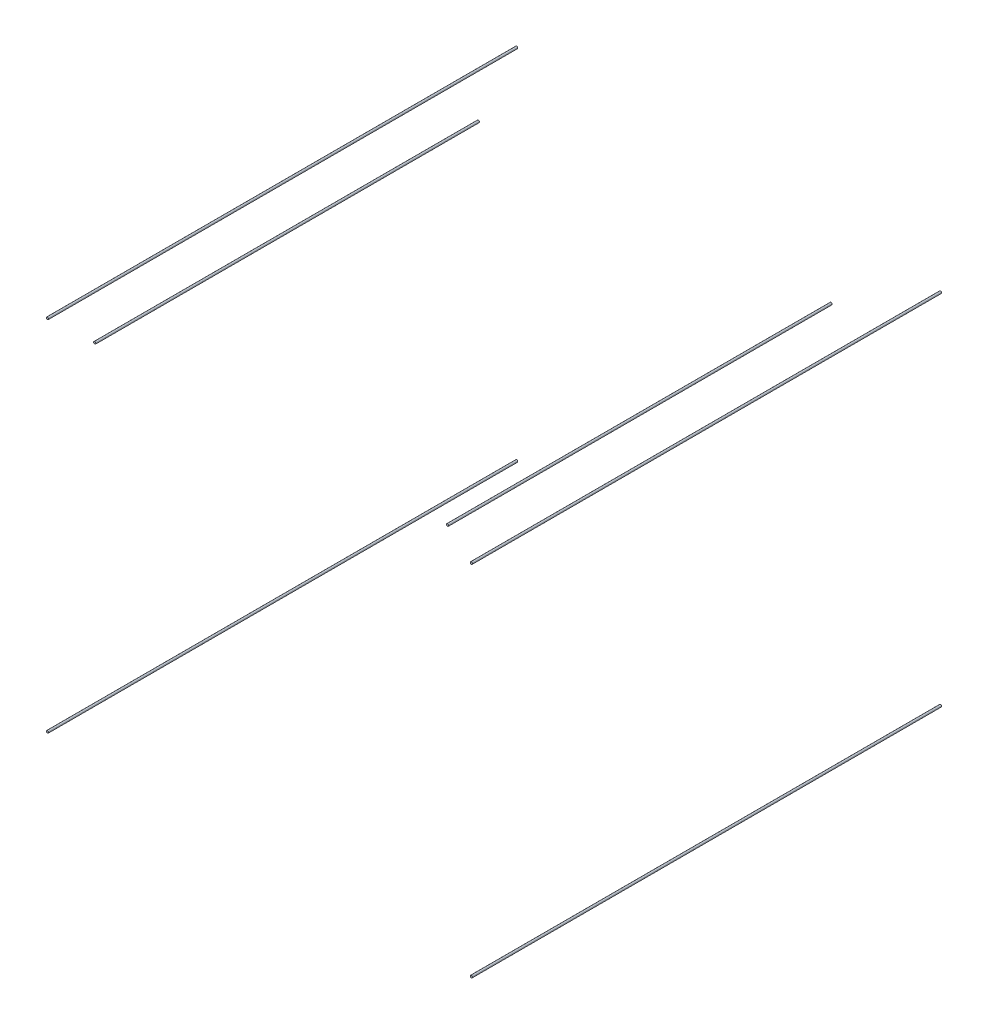
SolidWorks part; units mm, degrees
ref_plane "Front Plane" through (0, 0, 0) normal (0, 0, 1) x (1, 0, 0)
ref_plane "Top Plane" through (0, 0, 0) normal (0, 1, 0) x (1, 0, 0)
ref_plane "Right Plane" through (0, 0, 0) normal (1, 0, 0) x (0, 0, -1)
sketch "Sketch1" plane through (0, 0, 0) normal (0, 0, 1) x (1, 0, 0)
  circle A0 centre (3.5, 3.5) radius 0.15
  circle A1 centre (61.5, 3.5) radius 0.15
  circle A2 centre (3.5, 52.5) radius 0.15
  circle A3 centre (61.5, 52.5) radius 0.15
extrude "Line_1" add sketch "Sketch1" along normal blind 64.2
ref_plane "Plane_z10_1" through (0, 0, 10.1) normal (0, 0, 1) x (1, 0, 0)
sketch "Sketch2" plane through (0, 0, 10.1) normal (0, 0, 1) x (1, 0, 0)
  circle A0 centre (8.37, 51.23) radius 0.15
  circle A1 centre (56.63, 53.77) radius 0.15
extrude "Line_2" add sketch "Sketch2" along normal blind 52.5
